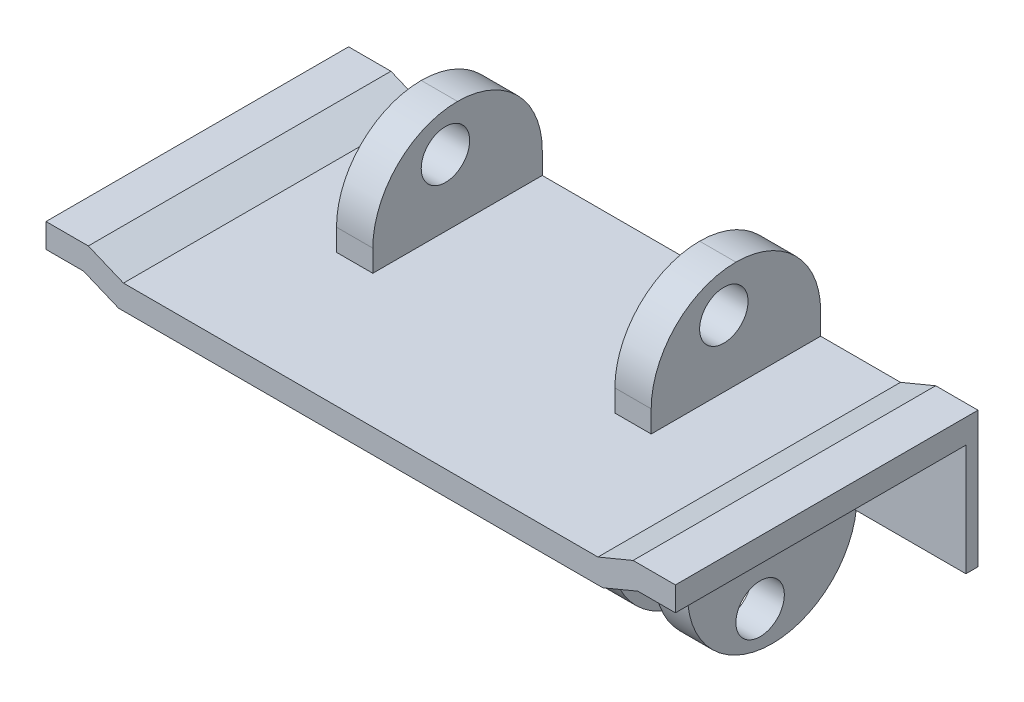
SolidWorks part; units mm, degrees
ref_plane "Front Plane" through (0, 0, 0) normal (0, 0, 1) x (1, 0, 0)
ref_plane "Top Plane" through (0, 0, 0) normal (0, 1, 0) x (1, 0, 0)
ref_plane "Right Plane" through (0, 0, 0) normal (1, 0, 0) x (0, 0, -1)
sketch "Sketch2" plane through (0, 0, 0) normal (0, 0, 1) x (1, 0, 0)
  line L0 (-5, 6) -> (-10, 6)
  line L1 (-5, 6) -> (5, 6) construction
  line L2 (-5, 6) -> (-5, -9) construction
  line L4 (5, 6) -> (5, -9) construction
  line L7 (-10, 6) -> (-10, -9)
  line L8 (-10, -9) -> (-5, -9)
  line L9 (-5, -9) -> (-5, 6)
  line L10 (0, 6) -> (0, -6) construction
  line L11 (10, -9) -> (5, -9)
  line L12 (10, 6) -> (10, -9)
  line L13 (5, 6) -> (10, 6)
  line L14 (5, -9) -> (5, 6)
  point P0 (0, 0)
  point P11 (0, 0)
  point P16 (0, 6)
  dimension "D1" = 15
  dimension "D2" = 10
  dimension "D3" = 5
extrude "Boss-Extrude1" add sketch "Sketch2" along normal blind 14
sketch "Sketch4" plane through (0, 0, 0) normal (0, 0, 1) x (1, 0, 0)
  line L0 (0, 0) -> (0, 50000) construction
  line L1 (-6.1796, 6) -> (49993.8204, 6) construction
  line L2 (-10, 6) -> (-20, 6)
  line L3 (10, 6) -> (20, 6)
  line L4 (-20, 6) -> (-22.9016, 7.2064)
  line L5 (-22.9016, 7.2064) -> (-26, 7.2064)
  line L6 (-10, 8) -> (-19.6008, 8)
  line L7 (-19.6008, 8) -> (-22.5024, 9.2064)
  line L8 (-22.5024, 9.2064) -> (-26, 9.2064)
  line L9 (-26, 9.2064) -> (-26, 7.2064)
  line L10 (-10, 6) -> (10, 6)
  line L11 (-10, 8) -> (10, 8)
  line L12 (10, 8) -> (19.6008, 8)
  line L13 (19.6008, 8) -> (22.5024, 9.2064)
  line L14 (20, 6) -> (22.9016, 7.2064)
  line L15 (22.9016, 7.2064) -> (26, 7.2064)
  line L16 (26, 9.2064) -> (26, 7.2064)
  line L17 (22.5024, 9.2064) -> (26, 9.2064)
  point P19 (0, 6)
  point P20 (0, 8)
  dimension "D1" = 10
  dimension "D3" = 6
  dimension "D2" = 2
extrude "Boss-Extrude3" add sketch "Sketch4" along normal blind 25
sketch "Sketch9" plane through (0, 0, 14) normal (0, 0, 1) x (1, 0, 0)
  line L0 (-10, -9) -> (-5, -9) construction
  line L1 (-5, 6) -> (-7.5, 6)
  line L2 (-5, 6) -> (-5, -9)
  line L3 (-5, -9) -> (-7.5, -9)
  line L4 (-7.5, 6) -> (-7.5, -9)
  line L5 (0, 7.972) -> (0, -7.972) construction
  line L6 (5, -9) -> (7.5, -9)
  line L7 (7.5, 6) -> (7.5, -9)
  line L8 (5, 6) -> (7.5, 6)
  line L9 (5, 6) -> (5, -9)
  point P11 (0, 0)
  dimension "D1" = 2.5
extrude "Cut-Extrude1" [suppressed] cut sketch "Sketch9" against normal blind 10
sketch "Sketch5" plane through (0, 0, 0) normal (0, 0, 1) x (1, 0, 0)
  line L0 (-10, 4.6) -> (-10, 50004.6) construction
  line L1 (0, 0) -> (0, 50000) construction
  line L2 (-10, 8) -> (-10, 16.8)
  line L3 (19.6008, 8) -> (-19.6008, 8) construction
  line L4 (-10, 16.8) -> (-13, 16.8)
  line L5 (-13, 16.8) -> (-13, 8)
  line L6 (-13, 8) -> (-10, 8)
  line L7 (13, 8) -> (10, 8)
  line L8 (13, 16.8) -> (13, 8)
  line L9 (10, 16.8) -> (13, 16.8)
  line L10 (10, 8) -> (10, 16.8)
  dimension "D1" = 3
  dimension "D2" = 8.8
extrude "Boss-Extrude4" add sketch "Sketch5" along normal blind 14
sketch "Sketch7" plane through (0, 0, 0) normal (0, 0, 1) x (1, 0, 0)
  line L0 (-13, 5.6) -> (-13, -49994.4) construction
  line L1 (-19.6008, 5.6) -> (-19.6008, -49994.4) construction
  line L2 (-10.0004, -9) -> (49989.9996, -9) construction
  line L3 (-15.0004, 6) -> (-50015.0004, 6) construction
  line L4 (-16, 6) -> (-16, -9)
  line L5 (-16, -9) -> (-13, -9)
  line L6 (-13, -9) -> (-13, 6)
  line L7 (-13, 6) -> (-16, 6)
  line L8 (0, 0) -> (0, -50000) construction
  line L13 (0, -13.75) -> (0, 13.75) construction
  line L14 (13, -9) -> (13, 6)
  line L15 (16, -9) -> (13, -9)
  line L16 (16, 6) -> (16, -9)
  line L17 (13, 6) -> (16, 6)
  dimension "D1" = 3
extrude "Boss-Extrude5" add sketch "Sketch7" along normal blind 14
sketch "Sketch15" plane through (0, -9, 0) normal (0, -1, 0) x (1, 0, 0)
  line L16 (-10, 14) -> (-9.7, 14)
  line L17 (-10, 14) -> (-5, 14) construction
  line L18 (-10, 14) -> (-10, 0) construction
  line L19 (-9.7, 14) -> (-9.7, 0)
  line L20 (-10, 0) -> (-5, 0) construction
  line L21 (-9.7, 0) -> (-10, 0)
  line L22 (-10, 0) -> (-10, 14)
  line L23 (0, -13.75) -> (0, 13.75) construction
  line L24 (9.7, 0) -> (10, 0)
  line L25 (9.7, 14) -> (9.7, 0)
  line L26 (10, 14) -> (9.7, 14)
  line L27 (10, 0) -> (10, 14)
  line L28 (-13, 14) -> (-13.3, 14)
  line L29 (-16, 14) -> (-13, 14) construction
  line L30 (-13.3, 14) -> (-13.3, 0)
  line L31 (-16, 0) -> (-13, 0) construction
  line L32 (-13.3, 0) -> (-13, 0)
  line L33 (-13, 0) -> (-13, 14)
  line L34 (13.3, 0) -> (13, 0)
  line L35 (13.3, 14) -> (13.3, 0)
  line L36 (13, 14) -> (13.3, 14)
  line L37 (13, 0) -> (13, 14)
  dimension "D1" = 0.3
  dimension "D2" = 0.3
extrude "Cut-Extrude2" cut sketch "Sketch15" against normal up to surface (15 mm away) up to face at (0, 6, 8.1)
sketch "Sketch16" plane through (0, -9, 0) normal (0, -1, 0) x (1, 0, 0)
  line L0 (-5, 14) -> (-5.15, 14)
  line L1 (-9.7, 14) -> (-5, 14) construction
  line L2 (-5.15, 14) -> (-5.15, 0)
  line L3 (-9.7, 0) -> (-5, 0) construction
  line L4 (-5.15, 0) -> (-5, 0)
  line L5 (-5, 0) -> (-5, 14)
  line L6 (0, -13.75) -> (0, 13.75) construction
  line L7 (5.15, 0) -> (5, 0)
  line L8 (5.15, 14) -> (5.15, 0)
  line L9 (5, 14) -> (5.15, 14)
  line L10 (5, 0) -> (5, 14)
  dimension "D1" = 0.15
extrude "Cut-Extrude3" cut sketch "Sketch16" against normal up to surface (15 mm away) up to face at (0, 6, 8.1)
fillet "Fillet1" radius 7 8 edges at (7.425, -9, 0) (7.425, -9, 14) (-7.425, -9, 0) (-7.425, -9, 14) (-14.65, -9, 0) (-14.65, -9, 14) (14.65, -9, 0) (14.65, -9, 14)
hole_wizard "Ø4.0mm Dowel Hole2" positions "Sketch10" profile "Sketch11" hole size "Ø4.0" standard "ANSI Metric" end condition through all
sketch "Sketch10" plane through (16, 0, 0) normal (1, 0, 0) x (0, 0, -1)
  line L7 (-25, 6) -> (0, 6) construction
  line L9 (-14, -2) -> (-14, 6) construction
  point P0 (-8, -6)
  dimension "D1" = 6
  dimension "D2" = 12
sketch "Sketch11" plane through (16, -6, 8) normal (0, 1, 0) x (0, 0, -1)
  line L0 (0, 0) -> (0, 42)
  line L1 (0, 42) -> (2, 42)
  line L2 (2, 42) -> (2, 0)
  line L5 (2, 0) -> (0, 0)
  line L11 (0, -6.35) -> (0, 107.95) construction
  dimension "Thru Hole Dia." = 4
  dimension "Thru Hole Depth" = 42
fillet "Fillet2" radius 7 4 edges at (-11.5, 16.8, 0) (-11.5, 16.8, 14) (11.5, 16.8, 0) (11.5, 16.8, 14)
hole_wizard "Ø4.0mm Dowel Hole1" positions "Sketch12" profile "Sketch13" hole size "Ø4.0" standard "ANSI Metric"
sketch "Sketch12" plane through (13, 0, 0) normal (1, 0, 0) x (0, 0, -1)
  line L1 (-25, 8) -> (0, 8) construction
  line L2 (-25, 8) -> (0, 8)
  circle A8 centre (-8, -6) radius 2 construction
  circle A9 centre (-8, -6) radius 2
  point P10 (-8, 13.5)
  dimension "D1" = 5.5
sketch "Sketch13" plane through (13, 13.5, 8) normal (0, 1, 0) x (0, 0, -1)
  line L0 (0, 0) -> (0, 27.2017)
  line L1 (0, 27.2017) -> (2, 26)
  line L2 (2, 26) -> (2, 0)
  line L5 (2, 0) -> (0, 0)
  line L10 (0, 27.2017) -> (-2, 26) construction
  line L11 (0, -6.35) -> (0, 107.95) construction
  dimension "Hole Dia." = 4
  dimension "Hole Depth" = 26
  dimension "Drill Angle" = 118
sketch "Sketch14" plane through (0, 0, 0) normal (0, 0, 1) x (1, 0, 0)
  line L4 (0, 14.6739) -> (0, -14.6739) construction
  line L5 (-26, 7.2064) -> (-22.9016, 7.2064)
  line L6 (-26, 6) -> (-26, 7.2064)
  line L7 (-20, 6) -> (-26, 6)
  line L8 (-22.9016, 7.2064) -> (-20, 6)
  line L13 (-16, 6) -> (-20, 6)
  line L14 (-26, -2) -> (-26, 6)
  line L15 (-16, -2) -> (-26, -2)
  line L18 (-16, 6) -> (-16, -2)
  line L21 (16, 6) -> (16, -2)
  line L22 (16, -2) -> (26, -2)
  line L23 (26, -2) -> (26, 6)
  line L24 (16, 6) -> (20, 6)
  line L25 (22.9016, 7.2064) -> (20, 6)
  line L26 (20, 6) -> (26, 6)
  line L27 (26, 6) -> (26, 7.2064)
  line L28 (26, 7.2064) -> (22.9016, 7.2064)
  point P11 (0, 0)
extrude "Boss-Extrude6" add sketch "Sketch14" along normal blind 1 contours L8 L5 L6 L7 | L14 L13 L7 | L27 L28 L25 L26 | L26 L24 L21 L22 L23 region at (-23.6483, 6.5391, 0) region at (-21, 2, 0) region at (21, 2, 0) region at (23.6483, 6.5391, 0)
sketch "Sketch18" plane through (-5.15, 0, 0) normal (1, 0, 0) x (0, 0, -1)
  line L1 (-6.1109, -3.2351) -> (-9.4499, -2.9815)
  line L2 (-9.4499, -2.9815) -> (-11.339, -5.7464)
  line L6 (-4.661, -6.2536) -> (-6.1109, -3.2351)
  line L7 (-11.339, -5.7464) -> (-12.4661, -20.5879)
  line L8 (-4.661, -6.2536) -> (-5.788, -21.095)
  line L9 (-12.4661, -20.5879) -> (-5.788, -21.095)
  line L11 (-10.6141, -7.2557) -> (-9.8891, -8.7649) [skipped]
  line L12 (-8.2196, -8.8917) -> (-6.5501, -9.0185) [skipped]
  line L13 (-5.6055, -7.636) -> (-4.661, -6.2536) [skipped]
extrude "Cut-Extrude4" cut sketch "Sketch18" against normal blind 2.4
mirror "Mirror1" about plane through (0, 0, 0) normal (1, 0, 0) of "Cut-Extrude4"
